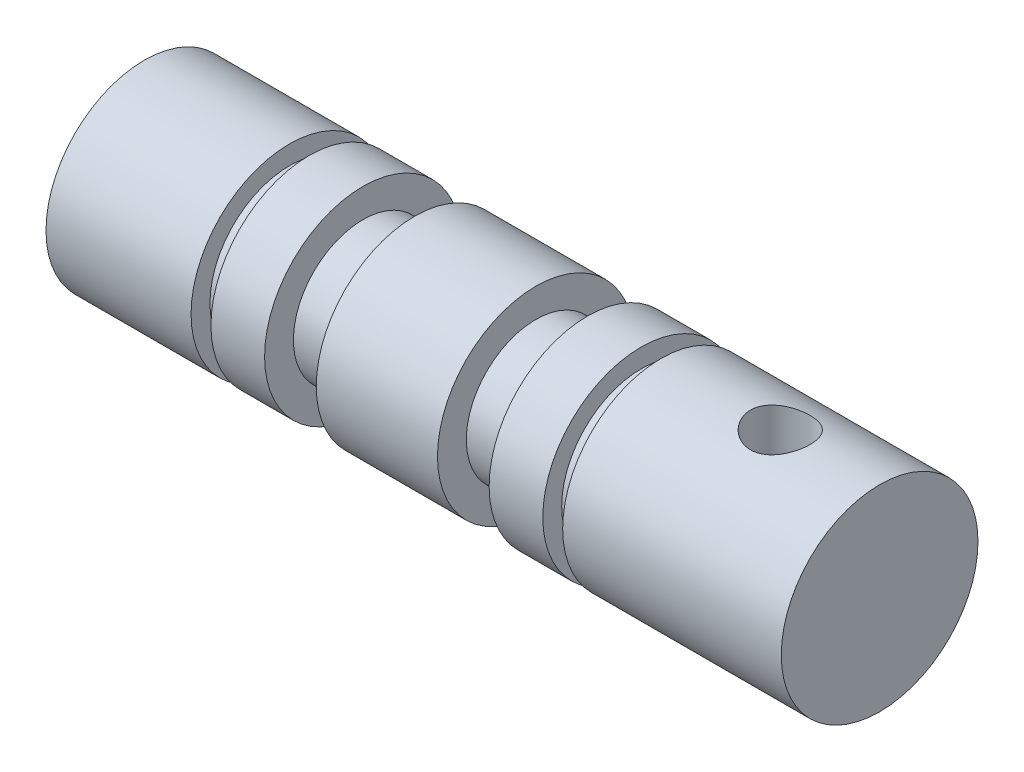
SolidWorks part; units mm, degrees
ref_plane "Спереди" through (0, 0, 0) normal (0, 0, 1) x (1, 0, 0)
ref_plane "Сверху" through (0, 0, 0) normal (0, 1, 0) x (1, 0, 0)
ref_plane "Справа" through (0, 0, 0) normal (1, 0, 0) x (0, 0, -1)
other "Configuration Table"
sketch "Эскиз1" plane through (0, 0, 0) normal (1, 0, 0) x (0, 0, -1)
  circle A0 centre (0, 0) radius 4.95
  circle A1 centre (0, 0) radius 3.5
  dimension "D1" = 9.9
  dimension "D2" = 7
extrude "Бобышка-Вытянуть1" add sketch "Эскиз1" along normal blind 37 contours A1 | A0 A1 region at (0, 0, 4.81) region at (0, 0, 0)
extrude "Вырез-Вытянуть1" cut sketch "Эскиз1<3>" along normal blind 2.6 from offset 11
sketch "Эскиз1<3>" plane through (0, 0, 0) normal (1, 0, 0) x (0, 0, -1) same geometry as "Эскиз1"
extrude "Вырез-Вытянуть2" cut sketch "Эскиз1<4>" along normal blind 2.6 from offset 19.7
sketch "Эскиз1<4>" plane through (0, 0, 0) normal (1, 0, 0) x (0, 0, -1) same geometry as "Эскиз1"
sketch "Эскиз2" plane through (0, 0, 0) normal (-1, 0, 0) x (0, 0, 1)
  circle A0 centre (0, 0) radius 1.5
  dimension "D1" = 3
extrude "Вырез-Вытянуть3" cut sketch "Эскиз2" against normal blind 10
sketch "Эскиз3" plane through (0, 0, 0) normal (0, 1, 0) x (1, 0, 0)
  line L0 (0, 4.95) -> (0, -4.95) construction
  circle A0 centre (4, 0) radius 1.25
  dimension "D1" = 2.5
  dimension "D2" = 4
extrude "Вырез-Вытянуть4" cut sketch "Эскиз3" against normal through all
sketch "Эскиз4" plane through (0, 0, 0) normal (-1, 0, 0) x (0, 0, 1)
  circle A0 centre (0, 0) radius 4
  circle A1 centre (0, 0) radius 4.95
  dimension "D1" = 8
extrude "Вырез-Вытянуть5" cut sketch "Эскиз4" along normal blind 1 from offset 8.3 offset against normal yes
extrude "Вырез-Вытянуть6" cut sketch "Эскиз4<2>" against normal blind 1 from offset 25 offset against normal yes
sketch "Эскиз4<2>" plane through (0, 0, 0) normal (-1, 0, 0) x (0, 0, 1) same geometry as "Эскиз4"
sketch "Эскиз5" plane through (0, 0, 0) normal (0, 1, 0) x (1, 0, 0)
  line L0 (37, -4.95) -> (37, 4.95) construction
  circle A0 centre (32, 0) radius 1.5
  point P2 (0, 0)
  dimension "D1" = 3
  dimension "D2" = 5
extrude "Вырез-Вытянуть7" cut sketch "Эскиз5" against normal through all both and the other way through all
